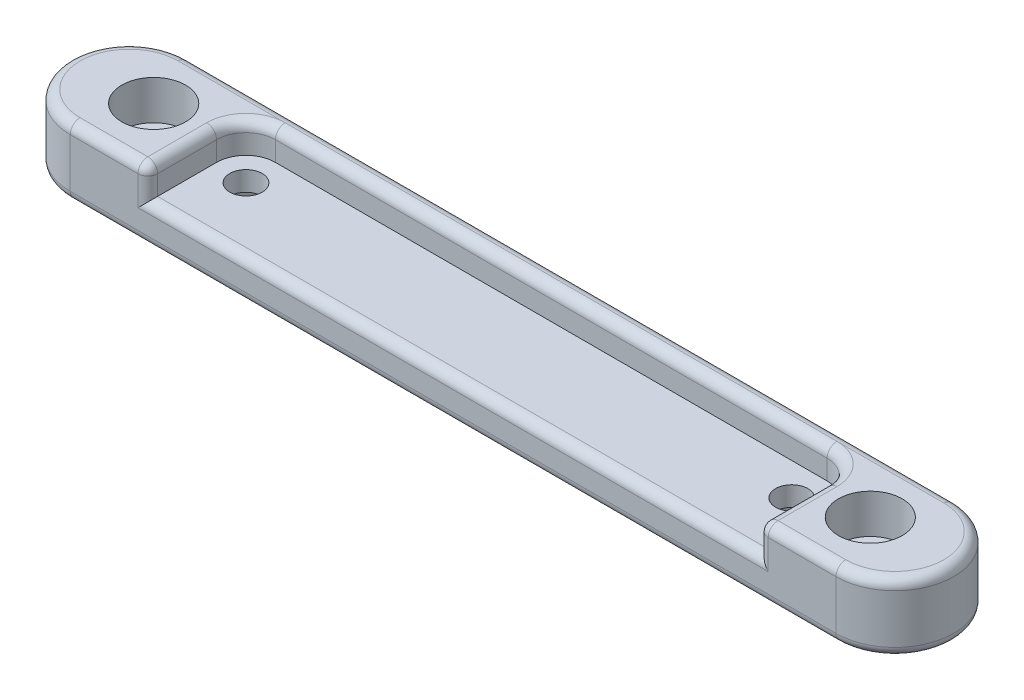
SolidWorks part; units mm, degrees
ref_plane "Plan de face" through (0, 0, 0) normal (0, 0, 1) x (1, 0, 0)
ref_plane "Plan de dessus" through (0, 0, 0) normal (0, 1, 0) x (1, 0, 0)
ref_plane "Plan de droite" through (0, 0, 0) normal (1, 0, 0) x (0, 0, -1)
sketch "Esquisse1" plane through (0, 0, 0) normal (0, 1, 0) x (1, 0, 0)
  line L0 (-27.8, 0) -> (27.8, 0) construction
  line L1 (0, 0) -> (0, 3.3) construction
  line L3 (-31.1, -6.7) -> (-31.1, 3.3)
  line L4 (-31.1, 3.3) -> (31.1, 3.3)
  line L5 (31.1, -6.7) -> (31.1, 3.3)
  line L6 (-31.1, -6.7) -> (31.1, -6.7)
  circle A0 centre (-27.8, 0) radius 1.65
  circle A1 centre (27.8, 0) radius 1.65
  point P4 (0, 0)
  point P7 (0, 0)
  dimension "D1" = 3.3
  dimension "D2" = 55.6
  dimension "D3" = 62.2
  dimension "D4" = 3.3
  dimension "D5" = 10
extrude "Boss.-Extru.1" add sketch "Esquisse1" along normal blind 4
sketch "Esquisse2" plane through (0, 4, 0) normal (0, 1, 0) x (1, 0, 0)
  line L0 (-31.1, -6.7) -> (-31.1, 3.3)
  line L1 (-31.1, 3.3) -> (31.1, 3.3)
  line L2 (31.1, 3.3) -> (31.1, -6.7)
  line L3 (31.1, -6.7) -> (33.5, -6.7)
  line L4 (33.5, -6.7) -> (33.5, 5.3)
  line L5 (33.5, 5.3) -> (-33.5, 5.3)
  line L6 (-33.5, 5.3) -> (-33.5, -6.7)
  line L7 (-33.5, -6.7) -> (-31.1, -6.7)
  dimension "D1" = 67
  dimension "D2" = 2
extrude "Boss.-Extru.2" add sketch "Esquisse2" along normal blind 3 and the other way up to surface (4 mm away) other way up to face at (-27.8, 0, 1.65)
fillet "Congé1" radius 3 2 edges at (31.1, 5.5, -3.3) (-31.1, 5.5, -3.3)
sketch "Esquisse3" plane through (0, 7, 0) normal (0, 1, 0) x (1, 0, 0)
  line L0 (0, 5.3) -> (0, -6.7) construction
  line L1 (33.5, 5.3) -> (-33.5, 5.3) construction
  line L2 (-31.1, -6.7) -> (31.1, -6.7) construction
  line L3 (-39, 5.3) -> (-39, -6.7) construction
  line L4 (-39, 5.3) -> (-33.5, 5.3)
  line L5 (-33.5, 5.3) -> (-33.5, -6.7)
  line L6 (-33.5, -6.7) -> (-39, -6.7)
  line L7 (33.5, 5.3) -> (33.5, -6.7)
  line L8 (39, 5.3) -> (33.5, 5.3)
  line L9 (33.5, -6.7) -> (39, -6.7)
  line L10 (-33.5, -0.7) -> (-36.5, -0.7) construction
  arc A0 (-39, 5.3) -> (-39, -6.7) centre (-39, -0.7) ccw
  arc A1 (39, 5.3) -> (39, -6.7) centre (39, -0.7) cw
  circle A2 centre (-36.5, -0.7) radius 1.65
  circle A3 centre (36.5, -0.7) radius 1.65
  dimension "D2" = 3.3
  dimension "D1" = 5.5
  dimension "D3" = 3
extrude "Boss.-Extru.3" add sketch "Esquisse3" against normal up to surface (7 mm away) up to face at (-27.8, 0, 1.65)
sketch "Esquisse5" plane through (0, 0, 0) normal (0, -1, 0) x (1, 0, 0)
  line L6 (-29.4454, 2.85) -> (-26.1546, 2.85)
  line L7 (-26.1546, 2.85) -> (-24.5091, 0)
  line L8 (-24.5091, 0) -> (-26.1546, -2.85)
  line L9 (-26.1546, -2.85) -> (-29.4454, -2.85)
  line L10 (-29.4454, -2.85) -> (-31.0909, 0)
  line L11 (-31.0909, 0) -> (-29.4454, 2.85)
  line L12 (-31.0909, 0) -> (-24.5091, 0) construction
  line L13 (26.1546, 2.85) -> (29.4454, 2.85)
  line L14 (29.4454, 2.85) -> (31.0909, 0)
  line L15 (31.0909, 0) -> (29.4454, -2.85)
  line L16 (29.4454, -2.85) -> (26.1546, -2.85)
  line L17 (26.1546, -2.85) -> (24.5091, 0)
  line L18 (24.5091, 0) -> (26.1546, 2.85)
  line L19 (24.5091, 0) -> (31.0909, 0) construction
  point P0 (-27.8, 0)
  point P1 (27.8, 0)
  point P2 (-27.8, 0)
  point P5 (-27.8, 0)
  point P12 (-27.8, 0)
  point P13 (27.8, 0)
  point P16 (27.8, 0)
  point P21 (27.8, 0)
  dimension "D1" = 120
  dimension "D2" = 120
  dimension "D3" = 5.7
  dimension "D4" = 5.7
extrude "Enlèv. mat.-Extru.1" cut sketch "Esquisse5" against normal blind 2
sketch "Esquisse6" plane through (0, 7, 0) normal (0, 1, 0) x (1, 0, 0)
  circle A0 centre (-36.5, -0.7) radius 3.25
  circle A1 centre (36.5, -0.7) radius 3.25
  dimension "D1" = 6.5
extrude "Enlèv. mat.-Extru.2" cut sketch "Esquisse6" against normal blind 4
fillet "Congé2" radius 1 17 edges at (31.1, 7, 3.2) (30.2213, 7, -2.4213) (0, 7, -3.3) (-30.2213, 7, -2.4213) (-45, 0, 0.7) (0, 0, -5.3) (45, 0, 0.7) (35.05, 7, 6.7) (45, 7, 0.7) (0, 7, -5.3) (-35.05, 7, 6.7) (31.1, 5.5, 6.7) (-31.1, 5.5, 6.7) (-31.1, 7, 3.2) (0, 4, 6.7) (0, 0, 6.7) (-45, 7, 0.7)
